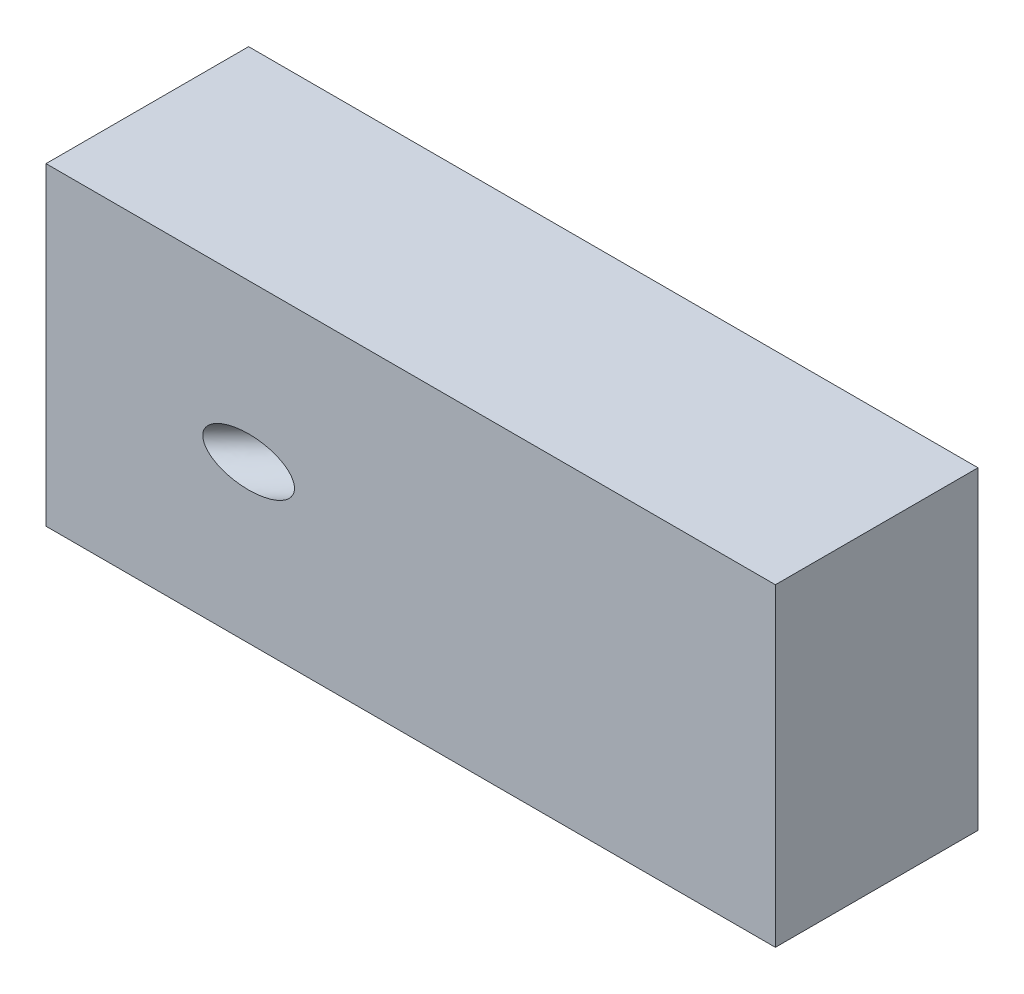
SolidWorks part; units mm, degrees
ref_plane "Plan de face" through (0, 0, 0) normal (0, 0, 1) x (1, 0, 0)
ref_plane "Plan de dessus" through (0, 0, 0) normal (0, 1, 0) x (1, 0, 0)
ref_plane "Plan de droite" through (0, 0, 0) normal (1, 0, 0) x (0, 0, -1)
sketch "Esquisse1" plane through (0, 0, 0) normal (0, 0, 1) x (1, 0, 0)
  line L1 (0, 7.75) -> (18, 7.75)
  line L2 (0, 7.75) -> (0, 0)
  line L3 (0, 0) -> (18, 0)
  line L4 (18, 7.75) -> (18, 0)
  dimension "D1" = 18
  dimension "D2" = 7.75
extrude "Boss.-Extru.1" add sketch "Esquisse1" along normal blind 5
ref_plane "Plan Milieu" through (0, 3.875, 0) normal (0, -1, 0) x (-1, 0, 0)
sketch "Esquisse10" plane through (0, 0, 5) normal (0, 0, 1) x (1, 0, 0)
  line L0 (-2.75, 3.875) -> (2.75, 3.875) construction
  line L1 (0, 7.75) -> (0, 0) construction
  point P0 (5, 3.875)
  point P1 (2, 3.875)
  point P6 (0, 0)
  dimension "D1" = 5
sketch "Esquisse11" plane through (0, 0, 0) normal (0, 0, -1) x (-1, 0, 0)
  line L0 (-2.75, 3.875) -> (2.75, 3.875) construction
  line L1 (0, 7.75) -> (0, 0) construction
  point P0 (-10, 3.875)
  point P1 (0, 0)
  point P4 (0, 0)
  dimension "D1" = 10
ref_axis "Axe3" through (5, 3.875, 5) along (0.7071, 0, -0.7071)
ref_axis "Axe5" [suppressed] through (5, 3.75, 5) along (0, 0, -1)
ref_plane "Plan2" through (5, 3.875, 5) normal (0.7071, 0, -0.7071) x (-0.7071, 0, -0.7071)
sketch "Esquisse13" plane through (5, 3.875, 5) normal (0.7071, 0, -0.7071) x (-0.7071, 0, -0.7071)
  ellipse E0 centre (0, 0) end of major axis (0.8, 0) minor radius 0.6
  dimension "D1" = 1.2
  dimension "D2" = 1.6
extrude "Enlèv. mat.-Extru.1" cut sketch "Esquisse13" along normal blind 15 and the other way blind 10
sketch "Esquisse15" plane through (0, 0, 0) normal (0, 0, -1) x (-1, 0, 0)
  line L0 (-18, 1.875) -> (-11.4792, 1.875) construction
  line L1 (-11.4792, 1.875) -> (-11.4792, 3.875) construction
  line L2 (-11.4792, 3.875) -> (-18, 3.875) construction
  line L3 (0, 0) -> (-18, 0) construction
  line L4 (-18, 0) -> (-18, 7.75) construction
  line L7 (-11.4792, 3.875) -> (-11.4792, 5.875) construction
  line L8 (-11.4792, 5.875) -> (-18, 5.875) construction
  circle A0 centre (-11.7292, 2.125) radius 0.25
  circle A1 centre (-11.7292, 5.625) radius 0.25
  dimension "D1" = 0.25
  dimension "D2" = 0.25
  dimension "D3" = 0.25
  dimension "D4" = 0.25
extrude "Boss.-Extru.3" add sketch "Esquisse15" along normal blind 0.5
